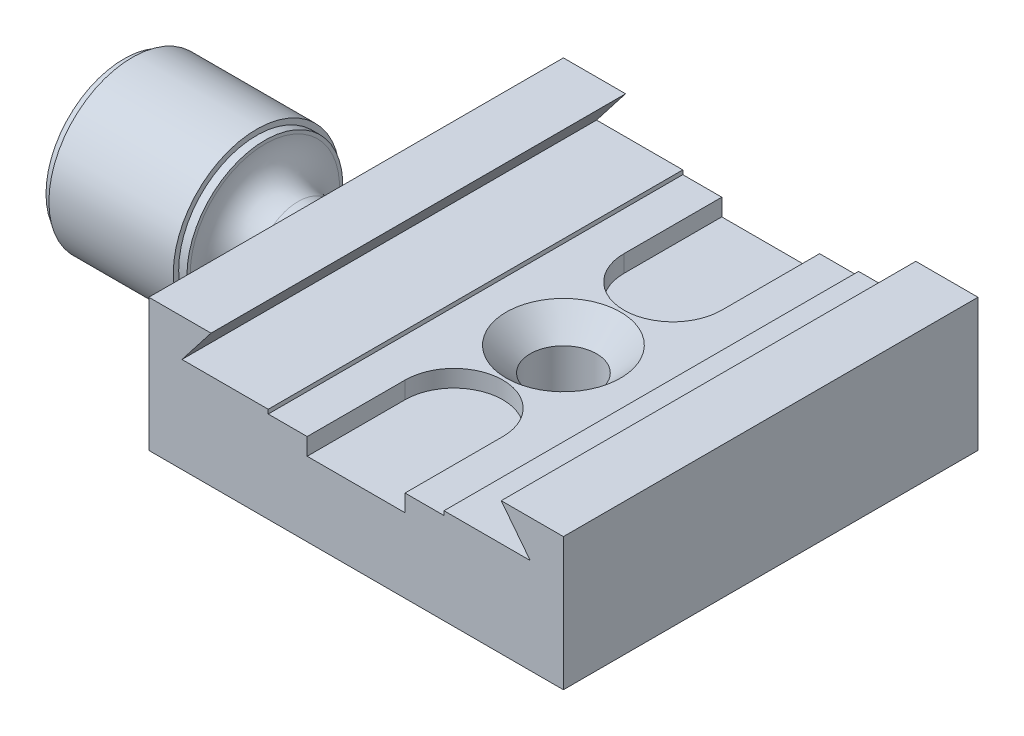
SolidWorks part; units mm, degrees
note: The reader was unsure of these and kept them because the rebuilt part matched: shared geometry of "草图1<4>", "草图1<5>", "草图8<3>".
ref_plane "前视基准面" through (0, 0, 0) normal (0, 0, 1) x (1, 0, 0)
ref_plane "上视基准面" through (0, 0, 0) normal (0, 1, 0) x (1, 0, 0)
ref_plane "右视基准面" through (0, 0, 0) normal (1, 0, 0) x (0, 0, -1)
sketch "草图1" plane through (0, 0, 0) normal (0, 1, 0) x (1, 0, 0)
  line L0 (-5.9, 13.2) -> (-5.9, 25)
  line L1 (-25, 25) -> (25, 25)
  line L2 (-25, 25) -> (-25, -25)
  line L3 (-25, -25) -> (25, -25)
  line L4 (25, 25) -> (25, -25)
  line L5 (-25, 25) -> (25, -25) construction
  line L6 (-25, -25) -> (25, 25) construction
  line L7 (5.9, 13.2) -> (5.9, 25)
  line L8 (0, 13.2) -> (0, 0) construction
  line L9 (5.9, -13.2) -> (5.9, -25)
  line L10 (-5.9, -13.2) -> (-5.9, -25)
  line L11 (0, -13.2) -> (0, 0) construction
  line L12 (-10.6, 25) -> (-10.6, -25)
  line L13 (10.6, 25) -> (10.6, -25)
  circle A0 centre (0, 0) radius 4
  circle A1 centre (0, 13.2) radius 5.9
  circle A2 centre (0, -13.2) radius 5.9
  point P0 (0, 0)
  point P22 (0, 0)
  dimension "D3" = 8
  dimension "D4" = 11.8
  dimension "D7" = 21.2
  dimension "D1" = 50
  dimension "D2" = 50
  dimension "D5" = 11.8
  dimension "D8" = 10.6
  dimension "D6" = 2
extrude "凸台-拉伸1" add sketch "草图1" along normal blind 8.94 contours A2 L10 L3 L9 | A2 | A1 | A1 L7 L1 L0
extrude "凸台-拉伸2" add sketch "草图1<4>" along normal blind 11 contours A2 L9 L3 L13 L1 L7 A1 L0 L12 L10 A0
sketch "草图1<4>" plane through (0, 0, 0) normal (0, 1, 0) x (1, 0, 0) same geometry as "草图1"
extrude "凸台-拉伸3" add sketch "草图1<5>" along normal blind 16 contours L1 L13 L3 L4 | L12 L1 L2 L3
sketch "草图1<5>" plane through (0, 0, 0) normal (0, 1, 0) x (1, 0, 0) same geometry as "草图1"
sketch "草图2" plane through (0, 0, 25) normal (0, 0, 1) x (1, 0, 0)
  line L0 (-17.5, 16) -> (-21, 11.5)
  line L1 (-25, 16) -> (-10.6, 16) construction
  line L2 (-21, 11.5) -> (21, 11.5)
  line L3 (21, 11.5) -> (17.5, 16)
  line L5 (-17.5, 16) -> (17.5, 16)
  line L7 (25, 16) -> (25, 0) construction
  line L8 (0, 16) -> (0, 11.5) construction
  dimension "D1" = 4.5
  dimension "D2" = 7.5
  dimension "D3" = 7.5
  dimension "D4" = 42
extrude "切除-拉伸1" cut sketch "草图2" against normal through all
sketch "草图3" plane through (0, 11, 0) normal (0, 1, 0) x (1, 0, 0)
  circle A0 centre (0, 0) radius 6.9
  dimension "D1" = 13.8
extrude "切除-拉伸2" cut sketch "草图3" against normal blind 16 draft 45
sketch "草图4" plane through (-25, 0, 0) normal (-1, 0, 0) x (0, 0, 1)
  line L0 (0, 5) -> (0, 0) construction
  line L1 (-25, 0) -> (25, 0) construction
  circle A0 centre (0, 5) radius 5
  dimension "D2" = 10
  dimension "D1" = 5
extrude "凸台-拉伸4" add sketch "草图4" along normal blind 11
sketch "草图5" plane through (-36, 0, 0) normal (-1, 0, 0) x (0, 0, 1)
  circle A0 centre (0, 5) radius 9.4
  dimension "D1" = 18.8
extrude "凸台-拉伸5" add sketch "草图5" along normal blind 1
sketch "草图6" plane through (-37, 0, 0) normal (-1, 0, 0) x (0, 0, 1)
  circle A0 centre (0, 5) radius 10.05
  dimension "D1" = 20.1
extrude "凸台-拉伸6" add sketch "草图6" along normal blind 15
sketch "草图7" plane through (-52, 0, 0) normal (-1, 0, 0) x (0, 0, 1)
  circle A0 centre (0, 5) radius 9.4
  dimension "D1" = 18.8
extrude "凸台-拉伸7" add sketch "草图7" along normal blind 1
fillet "圆角1" radius 4 1 edges at (-36, 5, 5)
sketch "草图8" plane through (0, 0, 0) normal (0, -1, 0) x (1, 0, 0)
  line L0 (0, 7.9) -> (0, -7.9) construction
  line L1 (2.5, 7.9) -> (2.5, -7.9)
  line L2 (-2.5, 7.9) -> (-2.5, -7.9)
  circle A0 centre (0, 0) radius 7
  arc A1 (2.5, 7.9) -> (-2.5, 7.9) centre (0, 7.9) ccw
  arc A2 (-2.5, -7.9) -> (2.5, -7.9) centre (0, -7.9) ccw
  point P5 (0, 0)
  circle M7 centre (0, 0) radius 4
  dimension "D1" = 14
  dimension "D2" = 2.5
  dimension "D3" = 15.8
extrude "切除-拉伸3" cut sketch "草图8" against normal blind 1.8 contours L2 A0 M7 | L1 A0 M7
extrude "切除-拉伸4" cut sketch "草图8<3>" against normal blind 2.8
sketch "草图8<3>" plane through (0, 0, 0) normal (0, -1, 0) x (1, 0, 0) same geometry as "草图8"
